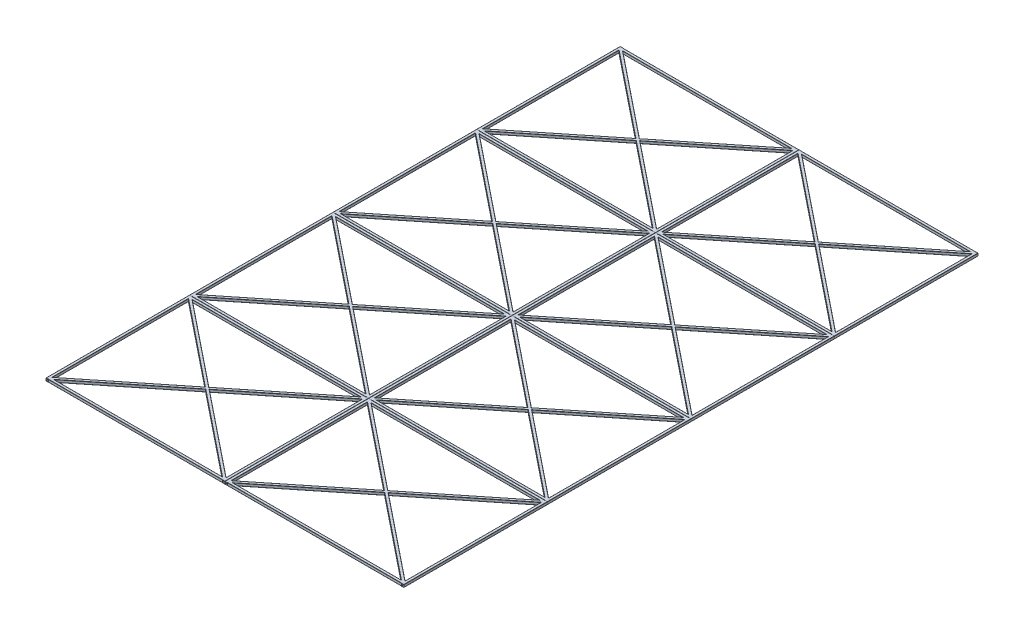
SolidWorks part; units mm, degrees
material "ASTM A500 Grade B"
ref_plane "Front Plane" through (0, 0, 0) normal (0, 0, 1) x (1, 0, 0)
ref_plane "Top Plane" through (0, 0, 0) normal (0, 1, 0) x (1, 0, 0)
ref_plane "Right Plane" through (0, 0, 0) normal (1, 0, 0) x (0, 0, -1)
sketch "Sketch1" plane through (0, 0, 0) normal (0, 1, 0) x (1, 0, 0)
  line L0 (1325, 0) -> (1325, -2125) construction
  line L1 (0, 0) -> (2650, 0)
  line L2 (0, 0) -> (0, -2125)
  line L3 (0, -2125) -> (2650, -2125)
  line L4 (2650, 0) -> (2650, -2125)
  line L5 (0, -1062.5) -> (2650, -1062.5) construction
  line L9 (0, 0) -> (2650, -2125) construction
  line L10 (2650, -2125) -> (2646.4748, -2133.2245) construction
  line L11 (1325, -1062.5) -> (1175.9048, -1248.4305) construction
  line L12 (2650, 0) -> (0, -2125) construction
  line L13 (1325, -1062.5) -> (1281.7828, -1008.6056) construction
  dimension "D1" = 2650
  dimension "D2" = 2125
sketch "Sketch2" plane through (0, 0, 0) normal (0, 0, 1) x (1, 0, 0)
  line L0 (5.3086, 16.1668) -> (32.7914, 16.1668)
  line L1 (2.54, 18.9354) -> (35.56, 18.9354)
  line L2 (0, 16.3954) -> (0, -16.6246)
  line L3 (2.54, -19.1646) -> (35.56, -19.1646)
  line L4 (38.1, 16.3954) -> (38.1, -16.6246)
  line L5 (35.3314, 13.6268) -> (35.3314, -13.856)
  line L6 (5.3086, -16.396) -> (32.7914, -16.396)
  line L7 (2.7686, 13.6268) -> (2.7686, -13.856)
  line L8 (2.7686, 16.1668) -> (2.7686, -16.396) construction
  line L9 (2.7686, -16.396) -> (35.3314, -16.396) construction
  line L10 (35.3314, 16.1668) -> (35.3314, -16.396) construction
  line L11 (38.1, 18.9354) -> (38.1, -19.1646) construction
  line L12 (0, -19.1646) -> (38.1, -19.1646) construction
  line L13 (0, 18.9354) -> (0, -19.1646) construction
  line L14 (0, 18.9354) -> (38.1, 18.9354) construction
  line L15 (2.7686, 16.1668) -> (35.3314, 16.1668) construction
  arc A0 (2.7686, -13.856) -> (5.3086, -16.396) centre (5.3086, -13.856) ccw
  arc A1 (32.7914, -16.396) -> (35.3314, -13.856) centre (32.7914, -13.856) ccw
  arc A2 (38.1, -16.6246) -> (35.56, -19.1646) centre (35.56, -16.6246) cw
  arc A3 (2.54, -19.1646) -> (0, -16.6246) centre (2.54, -16.6246) cw
  arc A4 (0, 16.3954) -> (2.54, 18.9354) centre (2.54, 16.3954) cw
  arc A5 (38.1, 16.3954) -> (35.56, 18.9354) centre (35.56, 16.3954) ccw
  arc A6 (35.3314, 13.6268) -> (32.7914, 16.1668) centre (32.7914, 13.6268) ccw
  arc A7 (2.7686, 13.6268) -> (5.3086, 16.1668) centre (5.3086, 13.6268) cw
  point P17 (38.1, -19.1646)
  dimension "D4" = 2.54
  dimension "D3" = 2.7686
extrude "Boss-Extrude1" add sketch "Sketch2" along normal up to vertex (2125 mm away) up to point (0, 0, 2125)
ref_plane "Plane1" through (1325, 0, 0) normal (-1, 0, 0) x (0, 0, 1)
mirror "Mirror2" about plane through (1325, 0, 0) normal (-1, 0, 0) of bodies 101
sketch "Sketch3" plane through (2611.9, 0, 0) normal (-1, 0, 0) x (0, 0, 1)
  line L0 (2125, -19.1646) -> (0, -19.1646) construction
  line L1 (2.54, 18.9354) -> (35.56, 18.9354)
  line L2 (0, 16.3954) -> (0, -16.6246)
  line L3 (2.54, -19.1646) -> (35.56, -19.1646)
  line L4 (38.1, 16.3954) -> (38.1, -16.6246)
  line L5 (5.3086, 16.1668) -> (32.7914, 16.1668)
  line L6 (35.3314, 13.6268) -> (35.3314, -13.856)
  line L7 (5.3086, -16.396) -> (32.7914, -16.396)
  line L8 (2.7686, 13.6268) -> (2.7686, -13.856)
  line L9 (38.1, 18.9354) -> (38.1, -19.1646) construction
  line L10 (0, -19.1646) -> (38.1, -19.1646) construction
  line L11 (2.7686, -16.396) -> (35.3314, -16.396) construction
  line L12 (35.3314, 16.1668) -> (35.3314, -16.396) construction
  line L13 (2.7686, 16.1668) -> (2.7686, -16.396) construction
  line L14 (0, 18.9354) -> (0, -19.1646) construction
  line L15 (2.7686, 16.1668) -> (35.3314, 16.1668) construction
  line L16 (0, 18.9354) -> (38.1, 18.9354) construction
  arc A0 (38.1, -16.6246) -> (35.56, -19.1646) centre (35.56, -16.6246) cw
  arc A1 (32.7914, -16.396) -> (35.3314, -13.856) centre (32.7914, -13.856) ccw
  arc A2 (5.3086, -16.396) -> (2.7686, -13.856) centre (5.3086, -13.856) cw
  arc A3 (2.54, -19.1646) -> (0, -16.6246) centre (2.54, -16.6246) cw
  arc A4 (2.7686, 13.6268) -> (5.3086, 16.1668) centre (5.3086, 13.6268) cw
  arc A5 (0, 16.3954) -> (2.54, 18.9354) centre (2.54, 16.3954) cw
  arc A6 (38.1, 16.3954) -> (35.56, 18.9354) centre (35.56, 16.3954) ccw
  arc A7 (35.3314, 13.6268) -> (32.7914, 16.1668) centre (32.7914, 13.6268) ccw
  point P14 (38.1, -19.1646)
  dimension "D3" = 2.54
  dimension "D2" = 2.7686
extrude "Boss-Extrude2" add sketch "Sketch3" along normal up to surface (2573.8 mm away) up to face at (38.1, -0.1146, 1062.5)
ref_plane "Plane2" through (0, 0, 1062.5) normal (0, 0, 1) x (1, 0, 0)
mirror "Mirror3" about plane through (0, 0, 1062.5) normal (0, 0, 1) of "Boss-Extrude2"
ref_plane "Plane8" through (1325, 0, 1062.5) normal (-0.7802, 0, -0.6256) x (-0.6256, 0, 0.7802)
sketch "Sketch8" plane through (1325, 0, 1062.5) normal (-0.7802, 0, -0.6256) x (-0.6256, 0, 0.7802)
  line L1 (-16.51, 18.9354) -> (16.51, 18.9354)
  line L2 (-19.05, 16.3954) -> (-19.05, -16.6246)
  line L3 (-16.51, -19.1646) -> (16.51, -19.1646)
  line L4 (19.05, 16.3954) -> (19.05, -16.6246)
  line L6 (16.2814, 13.6268) -> (16.2814, -13.856)
  line L7 (-13.7414, -16.396) -> (13.7414, -16.396)
  line L8 (-16.2814, 13.6268) -> (-16.2814, -13.856)
  line L9 (-13.7414, 16.1668) -> (13.7414, 16.1668)
  line L10 (-19.05, -19.1646) -> (19.05, -19.1646) construction
  line L11 (-19.05, 18.9354) -> (-19.05, -19.1646) construction
  line L12 (-16.2814, -16.396) -> (16.2814, -16.396) construction
  line L13 (-16.2814, 16.1668) -> (-16.2814, -16.396) construction
  line L14 (19.05, 18.9354) -> (19.05, -19.1646) construction
  line L15 (16.2814, 16.1668) -> (16.2814, -16.396) construction
  line L16 (-19.05, 18.9354) -> (19.05, 18.9354) construction
  line L17 (-16.2814, 16.1668) -> (16.2814, 16.1668) construction
  arc A0 (-16.51, -19.1646) -> (-19.05, -16.6246) centre (-16.51, -16.6246) cw
  arc A1 (-13.7414, -16.396) -> (-16.2814, -13.856) centre (-13.7414, -13.856) cw
  arc A2 (16.51, -19.1646) -> (19.05, -16.6246) centre (16.51, -16.6246) ccw
  arc A3 (13.7414, -16.396) -> (16.2814, -13.856) centre (13.7414, -13.856) ccw
  arc A4 (19.05, 16.3954) -> (16.51, 18.9354) centre (16.51, 16.3954) ccw
  arc A5 (16.2814, 13.6268) -> (13.7414, 16.1668) centre (13.7414, 13.6268) ccw
  arc A6 (-19.05, 16.3954) -> (-16.51, 18.9354) centre (-16.51, 16.3954) cw
  arc A7 (-16.2814, 13.6268) -> (-13.7414, 16.1668) centre (-13.7414, 13.6268) cw
  dimension "D4" = 2.54
  dimension "D2" = 19.05
  dimension "D3" = 2.7686
extrude "Boss-Extrude5" add sketch "Sketch8" against normal up to body and the other way up to body
ref_plane "Plane9" through (287.8812, 0, -230.8481) normal (0.7802, 0, -0.6256) x (-0.6256, 0, -0.7802)
sketch "Sketch9" plane through (287.8812, 0, -230.8481) normal (0.7802, 0, -0.6256) x (-0.6256, 0, -0.7802)
  line L1 (-1674.3293, 18.9354) -> (-1641.3093, 18.9354)
  line L2 (-1676.8693, 16.3954) -> (-1676.8693, -16.6246)
  line L3 (-1674.3293, -19.1646) -> (-1641.3093, -19.1646)
  line L4 (-1638.7693, 16.3954) -> (-1638.7693, -16.6246)
  line L5 (-1656.2303, -19.1646) -> (-1635.5732, -19.1646) construction
  line L6 (-1671.5607, 16.1668) -> (-1644.0779, 16.1668)
  line L7 (-1641.5379, 13.6268) -> (-1641.5379, -13.856)
  line L8 (-1671.5607, -16.396) -> (-1644.0779, -16.396)
  line L9 (-1674.1007, 13.6268) -> (-1674.1007, -13.856)
  line L10 (-1676.8693, -19.1646) -> (-1638.7693, -19.1646) construction
  line L11 (-1638.7693, 18.9354) -> (-1638.7693, -19.1646) construction
  line L12 (-1674.1007, -16.396) -> (-1641.5379, -16.396) construction
  line L13 (-1641.5379, 16.1668) -> (-1641.5379, -16.396) construction
  line L14 (-1676.8693, 18.9354) -> (-1638.7693, 18.9354) construction
  line L15 (-1674.1007, 16.1668) -> (-1641.5379, 16.1668) construction
  line L16 (-1676.8693, 18.9354) -> (-1676.8693, -19.1646) construction
  line L17 (-1674.1007, 16.1668) -> (-1674.1007, -16.396) construction
  arc A0 (-1641.3093, -19.1646) -> (-1638.7693, -16.6246) centre (-1641.3093, -16.6246) ccw
  arc A1 (-1644.0779, -16.396) -> (-1641.5379, -13.856) centre (-1644.0779, -13.856) ccw
  arc A2 (-1638.7693, 16.3954) -> (-1641.3093, 18.9354) centre (-1641.3093, 16.3954) ccw
  arc A3 (-1641.5379, 13.6268) -> (-1644.0779, 16.1668) centre (-1644.0779, 13.6268) ccw
  arc A4 (-1676.8693, -16.6246) -> (-1674.3293, -19.1646) centre (-1674.3293, -16.6246) ccw
  arc A5 (-1671.5607, -16.396) -> (-1674.1007, -13.856) centre (-1671.5607, -13.856) cw
  arc A6 (-1676.8693, 16.3954) -> (-1674.3293, 18.9354) centre (-1674.3293, 16.3954) cw
  arc A7 (-1674.1007, 13.6268) -> (-1671.5607, 16.1668) centre (-1671.5607, 13.6268) cw
  point P0 (-1657.8193, 0)
  point P17 (-1638.7693, -19.1646)
  dimension "D4" = 2.54
  dimension "D2" = 19.05
  dimension "D3" = 2.7686
ref_plane "Plane10" through (386.9603, 0, -310.2983) normal (0.7802, 0, -0.6256) x (-0.6256, 0, -0.7802)
sketch "Sketch11" plane through (386.9603, 0, -310.2983) normal (0.7802, 0, -0.6256) x (-0.6256, 0, -0.7802)
  line L1 (-1674.3293, 18.9354) -> (-1641.3093, 18.9354)
  line L2 (-1676.8693, 16.3954) -> (-1676.8693, -16.6246)
  line L3 (-1674.3293, -19.1646) -> (-1641.3093, -19.1646)
  line L4 (-1638.7693, 16.3954) -> (-1638.7693, -16.6246)
  line L6 (-1671.5607, 16.1668) -> (-1644.0779, 16.1668)
  line L7 (-1641.5379, 13.6268) -> (-1641.5379, -13.856)
  line L8 (-1671.5607, -16.396) -> (-1644.0779, -16.396)
  line L9 (-1674.1007, 13.6268) -> (-1674.1007, -13.856)
  line L10 (-1676.8693, -19.1646) -> (-1638.7693, -19.1646) construction
  line L11 (-1638.7693, 18.9354) -> (-1638.7693, -19.1646) construction
  line L12 (-1674.1007, -16.396) -> (-1641.5379, -16.396) construction
  line L13 (-1641.5379, 16.1668) -> (-1641.5379, -16.396) construction
  line L14 (-1676.8693, 18.9354) -> (-1638.7693, 18.9354) construction
  line L15 (-1674.1007, 16.1668) -> (-1641.5379, 16.1668) construction
  line L16 (-1676.8693, 18.9354) -> (-1676.8693, -19.1646) construction
  line L17 (-1674.1007, 16.1668) -> (-1674.1007, -16.396) construction
  arc A0 (-1641.3093, -19.1646) -> (-1638.7693, -16.6246) centre (-1641.3093, -16.6246) ccw
  arc A1 (-1644.0779, -16.396) -> (-1641.5379, -13.856) centre (-1644.0779, -13.856) ccw
  arc A2 (-1638.7693, 16.3954) -> (-1641.3093, 18.9354) centre (-1641.3093, 16.3954) ccw
  arc A3 (-1641.5379, 13.6268) -> (-1644.0779, 16.1668) centre (-1644.0779, 13.6268) ccw
  arc A4 (-1676.8693, -16.6246) -> (-1674.3293, -19.1646) centre (-1674.3293, -16.6246) ccw
  arc A5 (-1671.5607, -16.396) -> (-1674.1007, -13.856) centre (-1671.5607, -13.856) cw
  arc A6 (-1676.8693, 16.3954) -> (-1674.3293, 18.9354) centre (-1674.3293, 16.3954) cw
  arc A7 (-1674.1007, 13.6268) -> (-1671.5607, 16.1668) centre (-1671.5607, 13.6268) cw
  point P0 (-1657.8193, 0)
  point P17 (-1638.7693, -19.1646)
  dimension "D4" = 2.54
  dimension "D2" = 19.05
  dimension "D3" = 2.7686
extrude "Boss-Extrude7" add sketch "Sketch11" against normal up to body and the other way up to body
ref_plane "Plane11" through (188.8021, 0, -151.3979) normal (0.7802, 0, -0.6256) x (-0.6256, 0, -0.7802)
sketch "Sketch12" plane through (188.8021, 0, -151.3979) normal (0.7802, 0, -0.6256) x (-0.6256, 0, -0.7802)
  line L1 (-1674.3293, 18.9354) -> (-1641.3093, 18.9354)
  line L2 (-1676.8693, 16.3954) -> (-1676.8693, -16.6246)
  line L3 (-1674.3293, -19.1646) -> (-1641.3093, -19.1646)
  line L4 (-1638.7693, 16.3954) -> (-1638.7693, -16.6246)
  line L6 (-1671.5607, 16.1668) -> (-1644.0779, 16.1668)
  line L7 (-1641.5379, 13.6268) -> (-1641.5379, -13.856)
  line L8 (-1671.5607, -16.396) -> (-1644.0779, -16.396)
  line L9 (-1674.1007, 13.6268) -> (-1674.1007, -13.856)
  line L10 (-1676.8693, -19.1646) -> (-1638.7693, -19.1646) construction
  line L11 (-1638.7693, 18.9354) -> (-1638.7693, -19.1646) construction
  line L12 (-1674.1007, -16.396) -> (-1641.5379, -16.396) construction
  line L13 (-1641.5379, 16.1668) -> (-1641.5379, -16.396) construction
  line L14 (-1676.8693, 18.9354) -> (-1638.7693, 18.9354) construction
  line L15 (-1674.1007, 16.1668) -> (-1641.5379, 16.1668) construction
  line L16 (-1676.8693, 18.9354) -> (-1676.8693, -19.1646) construction
  line L17 (-1674.1007, 16.1668) -> (-1674.1007, -16.396) construction
  arc A0 (-1641.3093, -19.1646) -> (-1638.7693, -16.6246) centre (-1641.3093, -16.6246) ccw
  arc A1 (-1644.0779, -16.396) -> (-1641.5379, -13.856) centre (-1644.0779, -13.856) ccw
  arc A2 (-1638.7693, 16.3954) -> (-1641.3093, 18.9354) centre (-1641.3093, 16.3954) ccw
  arc A3 (-1641.5379, 13.6268) -> (-1644.0779, 16.1668) centre (-1644.0779, 13.6268) ccw
  arc A4 (-1676.8693, -16.6246) -> (-1674.3293, -19.1646) centre (-1674.3293, -16.6246) ccw
  arc A5 (-1671.5607, -16.396) -> (-1674.1007, -13.856) centre (-1671.5607, -13.856) cw
  arc A6 (-1676.8693, 16.3954) -> (-1674.3293, 18.9354) centre (-1674.3293, 16.3954) cw
  arc A7 (-1674.1007, 13.6268) -> (-1671.5607, 16.1668) centre (-1671.5607, 13.6268) cw
  point P0 (-1657.8193, 0)
  point P17 (-1638.7693, -19.1646)
  dimension "D4" = 2.54
  dimension "D2" = 19.05
  dimension "D3" = 2.7686
extrude "Boss-Extrude8" add sketch "Sketch12" along normal up to body and the other way up to body
mirror "Mirror4" about plane through (35.56, -16.6246, 2125) normal (0, 0, -1) of bodies 109
mirror "Mirror5" about plane through (35.56, -16.6246, 4250) normal (0, 0, 1) of bodies 110
mirror "Mirror6" about plane through (2650, 16.3954, 2125) normal (-1, 0, 0) of bodies 111 110 109
mirror "Mirror7" about plane through (35.56, -16.6246, 6375) normal (0, 0, -1) of bodies 111 112
